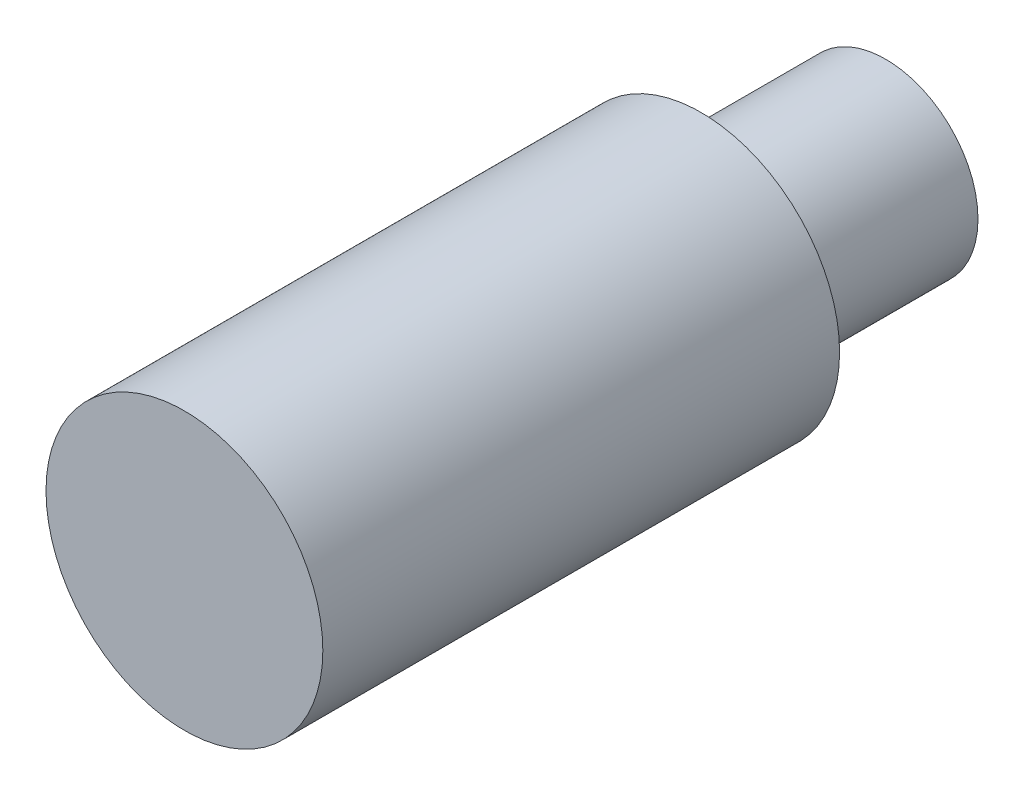
SolidWorks part; units mm, degrees
ref_plane "Front Plane" through (0, 0, 0) normal (0, 0, 1) x (1, 0, 0)
ref_plane "Top Plane" through (0, 0, 0) normal (0, 1, 0) x (1, 0, 0)
ref_plane "Right Plane" through (0, 0, 0) normal (1, 0, 0) x (0, 0, -1)
sketch "Sketch1" plane through (0, 0, 0) normal (0, 0, 1) x (1, 0, 0)
  circle A0 centre (0, 0) radius 5
  dimension "D1" = 10
extrude "Boss-Extrude1" add sketch "Sketch1" along normal blind 10
sketch "Sketch2" plane through (0, 0, 10) normal (0, 0, 1) x (1, 0, 0)
  circle A0 centre (0, 0) radius 7.5
  dimension "D1" = 15
extrude "Boss-Extrude2" add sketch "Sketch2" along normal blind 28
